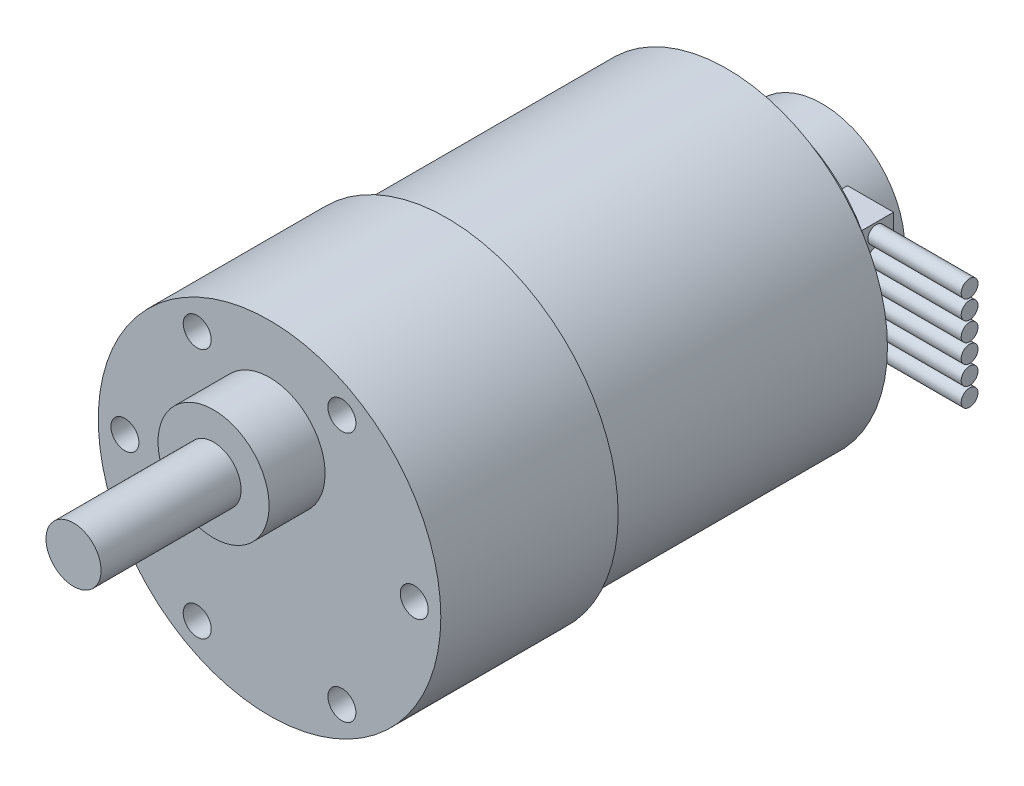
SolidWorks part; units mm, degrees
ref_plane "Front Plane" through (0, 0, 0) normal (0, 0, 1) x (1, 0, 0)
ref_plane "Top Plane" through (0, 0, 0) normal (0, 1, 0) x (1, 0, 0)
ref_plane "Right Plane" through (0, 0, 0) normal (1, 0, 0) x (0, 0, -1)
sketch "Sketch1" plane through (0, 0, 0) normal (0, 0, 1) x (1, 0, 0)
  circle A0 centre (0, 0) radius 18.35
  circle A1 centre (0, 0) radius 17.2
  dimension "D1" = 36.7
  dimension "D2" = 34.4
extrude "Boss-Extrude1" add sketch "Sketch1" along normal blind 19 contours A1 | A0 A1 | A1 | A0 region at (-17.831, 0, 0) region at (0, 0, 0)
extrude "Boss-Extrude2" add sketch "Sketch1<3>" against normal blind 30 contours A1 region at (0, 0, 0)
sketch "Sketch1<3>" plane through (0, 0, 0) normal (0, 0, 1) x (1, 0, 0) same geometry as "Sketch1"
ref_plane "Plane1" through (0, 0, 19) normal (0, 0, 1) x (1, 0, 0)
sketch "Sketch2" plane through (0, 0, 19) normal (0, 0, 1) x (1, 0, 0)
  line L0 (0, 18.35) -> (0, -18.35) construction
  line L1 (0, 13.05) -> (0, -18.35) construction
  line L2 (-17, 0) -> (17, 0) construction
  circle A0 centre (0, 0) radius 18.35 construction
  circle A1 centre (0, 0) radius 18.35 construction
  circle A2 centre (0, 7.1) radius 5.95
  circle A3 centre (0, 7.1) radius 2.95
  circle A4 centre (0, 0) radius 15.5 construction
  circle A7 centre (15.5, 0) radius 1.5
  circle A8 centre (7.75, -13.4234) radius 1.5
  circle A9 centre (-7.75, -13.4234) radius 1.5
  circle A10 centre (-15.5, 0) radius 1.5
  circle A11 centre (-7.75, 13.4234) radius 1.5
  circle A12 centre (7.75, 13.4234) radius 1.5
  dimension "D1" = 11.9
  dimension "D2" = 5.9
  dimension "D4" = 3
  dimension "D5" = 34
  dimension "D3" = 31.4
  dimension "D6" = 6
extrude "Cut-Extrude1" cut sketch "Sketch2" against normal blind 5 contours A11 | A12 | A7 | A8 | A9 | A10 region at (15.5, 0, 19) region at (7.75, -13.4234, 19) region at (-7.75, -13.4234, 19) region at (-15.5, 0, 19) region at (-7.75, 13.4234, 19) region at (7.75, 13.4234, 19)
extrude "Boss-Extrude3" add sketch "Sketch2<3>" along normal blind 6 contours A2 A3 | A3 region at (-5.7817, 7.1, 19) region at (0, 7.1, 19)
sketch "Sketch2<3>" plane through (0, 0, 19) normal (0, 0, 1) x (1, 0, 0) same geometry as "Sketch2"
extrude "Boss-Extrude4" add sketch "Sketch2<4>" along normal blind 21 contours A3 region at (0, 7.1, 19)
sketch "Sketch2<4>" plane through (0, 0, 19) normal (0, 0, 1) x (1, 0, 0) same geometry as "Sketch2"
ref_plane "Plane2" through (0, 0, -30) normal (0, 0, -1) x (-1, 0, 0)
sketch "Sketch3" plane through (0, 0, -30) normal (0, 0, -1) x (-1, 0, 0)
  circle A0 centre (0, 0) radius 13.25
  dimension "D1" = 26.5
extrude "Boss-Extrude5" add sketch "Sketch3" along normal blind 2.9
sketch "Sketch4" plane through (0, 0, -30) normal (0, 0, -1) x (-1, 0, 0)
  circle A0 centre (0, 0) radius 8.85
  dimension "D1" = 17.7
extrude "Boss-Extrude6" add sketch "Sketch4" along normal blind 10.2
sketch "Sketch5" plane through (0, 0, -30) normal (0, 0, -1) x (-1, 0, 0)
  line L0 (-11.25, 0) -> (-13.25, 0) construction
  line L1 (-5.75, -6.2) -> (-11.25, -6.2)
  line L2 (-5.75, -6.2) -> (-5.75, 6.2)
  line L3 (-5.75, 6.2) -> (-11.25, 6.2)
  line L4 (-11.25, -6.2) -> (-11.25, 6.2)
  line L5 (-5.75, -6.2) -> (-11.25, 6.2) construction
  line L6 (-5.75, 6.2) -> (-11.25, -6.2) construction
  circle A1 centre (0, 0) radius 13.25 construction
  circle A2 centre (0, 0) radius 13.25 construction
  point P0 (-8.5, 0)
  dimension "D1" = 12.4
  dimension "D2" = 5.5
  dimension "D3" = 2
extrude "Boss-Extrude7" add sketch "Sketch5" along normal blind 6.6
ref_plane "Plane3" through (11.25, 0, 0) normal (1, 0, 0) x (0, 0, -1)
sketch "Sketch6" plane through (11.25, 0, 0) normal (1, 0, 0) x (0, 0, -1)
  line L0 (34.75, 6.2) -> (34.75, -6.2) construction
  line L1 (36.6, 6.2) -> (32.9, 6.2) construction
  line L2 (32.9, -6.2) -> (36.6, -6.2) construction
  line L3 (34.75, 5.9714) -> (34.75, 6.2)
  line L4 (34.75, 4.1714) -> (34.75, 3.9429)
  line L5 (34.75, 2.1429) -> (34.75, 1.9143)
  line L6 (34.75, -4.1714) -> (34.75, -3.9429)
  line L7 (34.75, -2.1429) -> (34.75, -1.9143)
  line L8 (34.75, -0.1143) -> (34.75, 0.1143)
  line L9 (34.75, -5.9714) -> (34.75, -6.2)
  circle A0 centre (34.75, 5.0714) radius 0.9
  circle A1 centre (34.75, 3.0429) radius 0.9
  circle A2 centre (34.75, -3.0429) radius 0.9
  circle A3 centre (34.75, -1.0143) radius 0.9
  circle A4 centre (34.75, -5.0714) radius 0.9
  circle A5 centre (34.75, 1.0143) radius 0.9
  dimension "D1" = 1.8
extrude "Boss-Extrude8" add sketch "Sketch6" along normal blind 10 contours A0 L0 | L0 A0 | A1 L0 | L0 A1 | A5 L0 | L0 A5 | A3 L0 | L0 A3 | A2 L0 | L0 A2 | A4 L0 | L0 A4 region at (11.25, 5.0714, -35.132) region at (11.25, -5.0714, -35.132) region at (11.25, -5.0714, -34.368) region at (11.25, -3.0429, -35.132) region at (11.25, -3.0429, -34.368) region at (11.25, -1.0143, -35.132) region at (11.25, -1.0143, -34.368) region at (11.25, 1.0143, -35.132) region at (11.25, 1.0143, -34.368) region at (11.25, 3.0429, -35.132) region at (11.25, 3.0429, -34.368) region at (11.25, 5.0714, -34.368)
